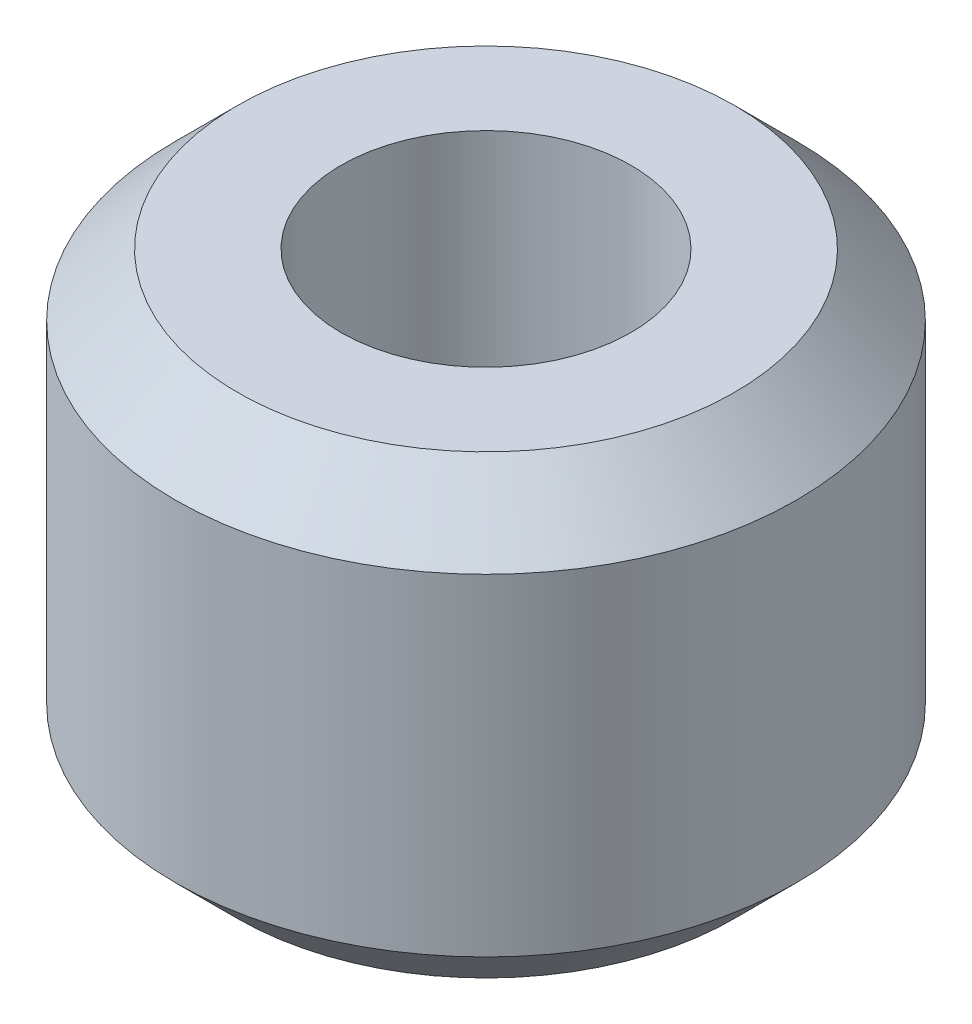
SolidWorks part; units mm, degrees
ref_plane "Front Plane" through (0, 0, 0) normal (0, 0, 1) x (1, 0, 0)
ref_plane "Top Plane" through (0, 0, 0) normal (0, 1, 0) x (1, 0, 0)
ref_plane "Right Plane" through (0, 0, 0) normal (1, 0, 0) x (0, 0, -1)
sketch "Sketch2" plane through (0, 0, 0) normal (0, 0, 1) x (1, 0, 0)
  line L0 (3.5, 11) -> (-3.5, 11) construction
  line L1 (3.5, 11) -> (-3.5, 11)
sketch "Sketch1" plane through (0, 0, 0) normal (0, 1, 0) x (1, 0, 0)
  circle A0 centre (0, 0) radius 3.5
  circle A1 centre (0, 0) radius 7.5
  dimension "D1" = 7
  dimension "D2" = 15
extrude "Boss-Extrude1" add sketch "Sketch1" along normal up to vertex (11 mm away) up to point (3.5, 11, 0)
chamfer "Chamfer1" distance 1 angle 45 1 edges at (0, 0, 3.5)
chamfer "Chamfer2" distance 1.5 angle 45 2 edges at (0, 11, 7.5) (0, 0, 7.5)
